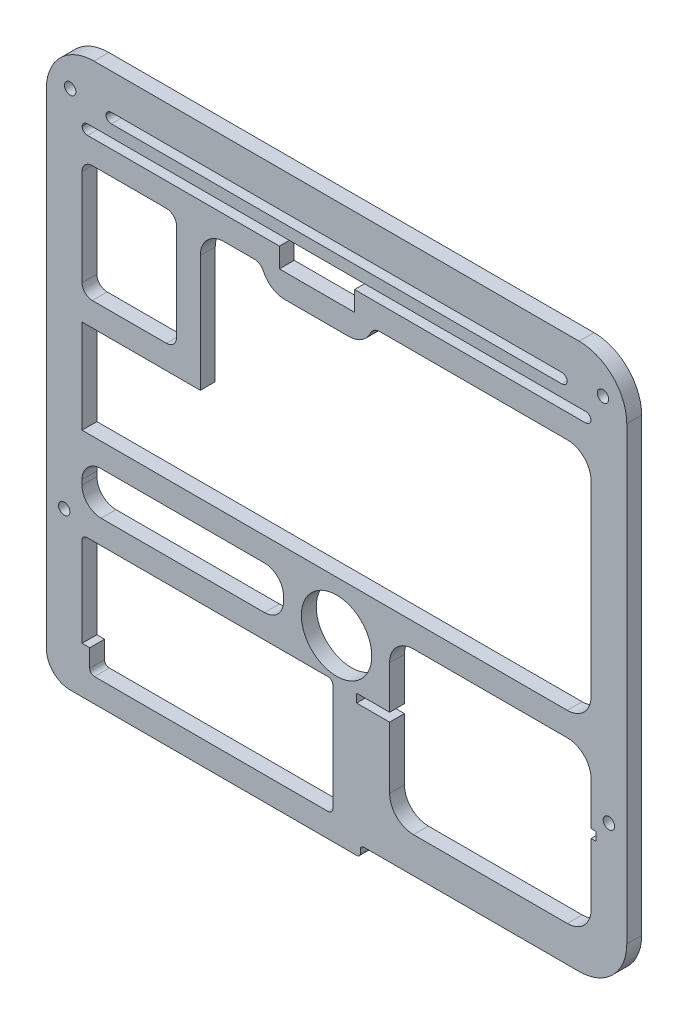
SolidWorks part; units mm, degrees
ref_plane "Front Plane" through (0, 0, 0) normal (0, 0, 1) x (1, 0, 0)
ref_plane "Top Plane" through (0, 0, 0) normal (0, 1, 0) x (1, 0, 0)
ref_plane "Right Plane" through (0, 0, 0) normal (1, 0, 0) x (0, 0, -1)
sketch "Sketch1" plane through (0, 0, 0) normal (0, 0, 1) x (1, 0, 0)
  line L0 (63.9883, 50.6392) -> (63.9883, 46.8292) construction
  line L1 (4.1102, -7.651) -> (66.0868, -7.651)
  line L2 (4.1102, -7.651) -> (4.1102, 50.6392)
  line L3 (4.1102, 50.6392) -> (66.0868, 50.6392)
  line L4 (66.0868, -7.651) -> (66.0868, 50.6392)
  line L5 (62.2768, 46.8292) -> (7.9202, 46.8292)
  line L6 (62.2768, 46.8292) -> (62.2768, -3.841)
  line L7 (62.2768, -3.841) -> (7.9202, -3.841)
  line L8 (7.9202, 46.8292) -> (7.9202, -3.841)
  line L9 (63.9883, 48.7342) -> (18.0707, 48.7342) construction
  line L10 (7.9202, 41.2855) -> (4.1102, 41.2855) construction
  line L11 (6.0152, 41.2855) -> (6.0152, 25.8577) construction
  line L12 (13.5248, -3.841) -> (13.5248, -7.651) construction
  line L13 (13.5248, -5.746) -> (21.1598, -5.746) construction
  line L14 (66.0868, 38.1916) -> (62.2768, 38.1916) construction
  line L15 (64.1818, 38.1916) -> (64.1818, 22.3321) construction
  line L16 (62.2768, 6.192) -> (62.2768, 41.7492) construction
  line L17 (7.9202, 36.7962) -> (7.9202, 1.239) construction
  line L22 (34.9556, 48.7342) -> (35.5018, 48.7342) construction
  line L23 (52.4244, -5.746) -> (51.8782, -5.746) construction
  dimension "D1" = 3.81
  dimension "D2" = 3.81
extrude "Boss-Extrude1" add sketch "Sketch1" along normal blind 1.5875
sketch "Sketch2" plane through (0, 0, 0) normal (0, 0, -1) x (-1, 0, 0)
  line L0 (-62.2768, -3.841) -> (-62.2768, 46.8292) construction
  line L1 (-62.2768, 15.868) -> (-7.9202, 15.868)
  line L2 (-62.2768, 15.868) -> (-62.2768, 13.328)
  line L3 (-62.2768, 13.328) -> (-7.9202, 13.328)
  line L4 (-7.9202, 15.868) -> (-7.9202, 13.328)
  line L5 (-7.9202, 46.8292) -> (-7.9202, -3.841) construction
  line L6 (-13.0532, 15.868) -> (-50.7532, 15.868) construction
  line L8 (-55.2788, 43.4256) -> (-16.9248, 43.4256) construction
  line L9 (-36.3812, 41.3174) -> (-29.6248, 41.3174) construction
  line L10 (-36.3812, 43.4256) -> (-36.3812, 41.3174) construction
  line L11 (-62.2768, 43.4256) -> (-37.0162, 43.4256)
  line L12 (-62.2768, 43.4256) -> (-62.2768, 40.8856)
  line L13 (-62.2768, 40.8856) -> (-38.9212, 40.8856)
  line L14 (-7.9202, 43.4256) -> (-7.9202, 40.8856)
  line L15 (-62.2768, 45.7624) -> (-7.9202, 45.7624)
  line L16 (-62.2768, 45.7624) -> (-62.2768, 44.4924)
  line L17 (-62.2768, 44.4924) -> (-7.9202, 44.4924)
  line L18 (-7.9202, 45.7624) -> (-7.9202, 44.4924)
  line L19 (-29.6248, 41.3174) -> (-29.6248, 43.4256) construction
  line L20 (-36.3812, 43.4256) -> (-36.3812, 41.3174) construction
  line L21 (-29.6248, 41.3174) -> (-29.6248, 43.4256) construction
  line L22 (-37.0162, 41.3174) -> (-37.0162, 43.4256)
  line L23 (-28.9898, 41.3174) -> (-37.0162, 41.3174)
  line L24 (-28.9898, 41.3174) -> (-28.9898, 43.4256)
  line L25 (-38.9212, 40.8856) -> (-38.9212, 38.7774)
  line L26 (-38.9212, 38.7774) -> (-27.0848, 38.7774)
  line L27 (-27.0848, 38.7774) -> (-27.0848, 40.8856)
  line L28 (-27.0848, 40.8856) -> (-7.9202, 40.8856)
  line L29 (-28.9898, 43.4256) -> (-7.9202, 43.4256)
  line L30 (-37.0162, 42.249) -> (-36.3812, 42.249) construction
  line L31 (-57.9086, 46.8292) -> (-57.9086, 45.7624) construction
  line L32 (-29.6248, 42.1673) -> (-28.9898, 42.1673) construction
  line L33 (-62.2768, 46.8292) -> (-7.9202, 46.8292) construction
  line L35 (-57.9086, 44.4924) -> (-57.9086, 43.4256) construction
  dimension "D1" = 2.54
  dimension "D2" = 1.905
  dimension "D3" = 2.54
  dimension "D4" = 1.905
  dimension "D5" = 1.27
  dimension "D6" = 0.635
extrude "Boss-Extrude2" add sketch "Sketch2" against normal up to surface (1.5875 mm away) up to face at (35.0985, 21.4941, 1.5875)
sketch "Sketch3" plane through (0, 0, 0) normal (0, 0, -1) x (-1, 0, 0)
  line L1 (-16.3032, 25.868) -> (-7.9202, 25.868) construction
  line L12 (-20.5532, 25.868) -> (-13.0532, 25.868)
  line L13 (-13.0532, 25.868) -> (-7.9202, 25.868)
  line L14 (-7.9202, 40.8856) -> (-7.9202, 15.868) construction
  line L15 (-7.9202, 25.868) -> (-7.9202, 28.408)
  line L16 (-7.9202, 28.408) -> (-18.0132, 28.408)
  line L17 (-18.0132, 28.408) -> (-18.0132, 40.8856)
  line L18 (-27.0848, 40.8856) -> (-7.9202, 40.8856) construction
  line L19 (-18.0132, 40.8856) -> (-20.5532, 40.8856)
  line L20 (-20.5532, 40.8856) -> (-20.5532, 25.868)
  line M27 (-27.0848, 40.8856) -> (-7.9202, 40.8856)
  line M28 (-7.9202, 40.8856) -> (-7.9202, 15.868)
  dimension "D3" = 2.54
  dimension "D4" = 2.54
extrude "Boss-Extrude3" add sketch "Sketch3" against normal up to surface (1.5875 mm away) contours L20 L12 L13 L16 L17 M27 M28 region at (20.3569, 33.3768, 0) up to face at (35.0985, 46.2958, 1.5875)
sketch "Sketch4" plane through (0, 0, 0) normal (0, 0, -1) x (-1, 0, 0)
  line L0 (-62.2768, 13.328) -> (-7.9202, 13.328) construction
  line L1 (-40.7627, 13.328) -> (-29.4343, 13.328)
  line L2 (-40.7627, 13.328) -> (-40.7627, -3.841)
  line L3 (-40.7627, -3.841) -> (-29.4343, -3.841)
  line L4 (-29.4343, 13.328) -> (-29.4343, -3.841)
  line L5 (-7.9202, -3.841) -> (-62.2768, -3.841) construction
  line L6 (-38.8577, 10.4578) -> (-40.7627, 10.4578) construction
  line L7 (-31.3393, 10.4578) -> (-29.4343, 10.4578) construction
  dimension "D1" = 1.905
extrude "Boss-Extrude4" add sketch "Sketch4" against normal up to surface (1.5875 mm away) up to face at (12.9667, 34.6468, 1.5875)
sketch "Sketch5" plane through (0, 0, 0) normal (0, 0, -1) x (-1, 0, 0)
  line L1 (-8.7364, -6.254) -> (-34.6952, -6.254) construction
  line L2 (-8.7364, -6.254) -> (-8.7364, 6.2047) construction
  line L6 (-8.7364, 6.2047) -> (-34.6952, 6.2047) construction
  line L7 (-34.6952, -6.254) -> (-34.6952, 6.2047) construction
  line L8 (-8.7364, -6.254) -> (-34.6952, -6.254)
  line L9 (-8.7364, -6.254) -> (-8.7364, 6.2047)
  line L10 (-8.7364, 6.2047) -> (-34.6952, 6.2047)
  line L11 (-34.6952, -6.254) -> (-34.6952, 6.2047)
  circle A1 centre (-35.0985, 10.4578) radius 3.7592 construction
  circle A2 centre (-35.0985, 10.4578) radius 3.7592
extrude "Cut-Extrude1" cut sketch "Sketch5" against normal up to surface (1.5875 mm away) up to face at (51.5197, 4.7435, 1.5875)
sketch "Sketch10" plane through (0, 0, 1.5875) normal (0, 0, 1) x (1, 0, 0)
  line L0 (29.4343, 13.328) -> (29.4343, 6.2047) construction
  line L1 (7.9202, 6.2047) -> (29.4343, 6.2047)
  line L2 (7.9202, 6.2047) -> (7.9202, 8.7447)
  line L3 (7.9202, 8.7447) -> (29.4343, 8.7447)
  line L4 (29.4343, 6.2047) -> (29.4343, 8.7447)
  line L5 (7.9202, 13.328) -> (7.9202, -3.841) construction
  line L6 (34.6952, 6.2047) -> (29.4343, 6.2047) construction
  dimension "D1" = 2.54
extrude "Boss-Extrude5" add sketch "Sketch10" against normal up to surface (1.5875 mm away) up to face at (20.1965, 2.3595, 0)
fillet "Fillet1" radius 5.08 3 edges at (66.0868, -7.651, 0.7937) (4.1102, 50.6392, 0.7937) (66.0868, 50.6392, 0.7937)
fillet "Fillet2" radius 2.54 5 edges at (20.5532, 40.8856, 0.7937) (27.0848, 38.7774, 0.7937) (62.2768, 40.8856, 0.7937) (62.2768, 15.868, 0.7937) (38.9212, 38.7774, 0.7937)
fillet "Fillet3" radius 1.0922 6 edges at (7.9202, 28.408, 0.7937) (18.0132, 28.408, 0.7937) (7.9202, 40.8856, 0.7937) (18.0132, 40.8856, 0.7937) (27.0848, 40.8856, 0.7937) (38.9212, 40.8856, 0.7937)
fillet "Fillet4" radius 0.5842 4 edges at (7.9202, 43.4256, 0.7937) (7.9202, 44.4924, 0.7937) (62.2768, 44.4924, 0.7937) (62.2768, 43.4256, 0.7937)
sketch "Sketch6" plane through (0, 0, 0) normal (0, 0, -1) x (-1, 0, 0)
  line L0 (-9.5532, 24.368) -> (-9.5532, 17.368) construction
  line L1 (-9.5532, 24.368) -> (-9.5532, 17.368)
  line L2 (-11.0532, 25.868) -> (-9.5532, 24.368) construction
  line L3 (-11.0532, 25.868) -> (-9.5532, 24.368)
  line L4 (-11.0532, 25.868) -> (-11.0532, 15.868)
  line L6 (-13.0532, 17.368) -> (-13.0532, 15.868)
  line L7 (-13.0532, 15.868) -> (-11.0532, 15.868)
  line L8 (-11.0532, 15.868) -> (-9.5532, 17.368)
  line L9 (-9.5532, 17.368) -> (-13.0532, 17.368)
  line L12 (-11.0532, 15.868) -> (-9.5532, 17.368)
  circle A0 centre (-63.5468, 46.8292) radius 0.6096 construction
  circle A1 centre (-6.6502, 46.8292) radius 0.6096 construction
  circle A2 centre (-64.1818, 7.6638) radius 0.6096 construction
  circle A3 centre (-6.0152, 7.6638) radius 0.6096 construction
  circle A4 centre (-63.5468, 46.8292) radius 0.6096
  circle A5 centre (-6.6502, 46.8292) radius 0.6096
  circle A6 centre (-64.1818, 7.6638) radius 0.6096
  circle A7 centre (-6.0152, 7.6638) radius 0.6096
  dimension "D1" = 0
extrude "Cut-Extrude2" cut sketch "Sketch6" against normal up to surface (1.5875 mm away) up to face at (17.1172, -1.2967, 1.5875)
sketch "Sketch9" plane through (0, 0, 1.5875) normal (0, 0, 1) x (1, 0, 0)
  line L4 (62.813, 6.2047) -> (37.2352, 6.2047)
  line L5 (37.2352, 6.2047) -> (37.2352, 5.2903)
  line L6 (37.2352, 5.2903) -> (62.813, 5.2903)
  line L7 (62.813, 5.2903) -> (62.813, 6.2047)
  line L8 (62.813, 6.2047) -> (37.2352, 6.2047)
  line L9 (37.2352, 6.2047) -> (37.2352, 5.2903)
  line L10 (37.2352, 5.2903) -> (62.813, 5.2903)
  line L11 (62.813, 5.2903) -> (62.813, 6.2047)
  dimension "D1" = 0
extrude "Cut-Extrude3" cut sketch "Sketch9" against normal up to surface (1.5875 mm away) up to face at (5.4056, 7.6638, 0)
fillet "Fillet6" radius 0.508 4 edges at (34.6952, 6.2047, 0.7937) (34.6952, -6.254, 0.7937) (8.7364, -6.254, 0.7937) (7.9202, 6.2047, 0.7937)
sketch "Sketch11" plane through (0, 0, 1.5875) normal (0, 0, 1) x (1, 0, 0)
  line L0 (9.2444, -6.254) -> (34.1872, -6.254) construction
  line L1 (4.1102, -7.651) -> (37.6385, -7.651)
  line L2 (4.1102, -7.651) -> (4.1102, -8.794)
  line L3 (4.1102, -8.794) -> (37.6385, -8.794)
  line L4 (37.6385, -7.651) -> (37.6385, -8.794)
  line L5 (35.0985, 14.217) -> (35.0985, -22.2214) construction
  circle A0 centre (35.0985, 10.4578) radius 3.7592 construction
  dimension "D1" = 2.54
  dimension "D2" = 2.54
extrude "Boss-Extrude6" add sketch "Sketch11" against normal up to surface (1.5875 mm away) up to face at (51.0212, 5.4129, 0)
fillet "Fillet7" radius 2.54 1 edges at (4.1102, -8.794, 0.7937)
fillet "Fillet8" radius 0.381 2 edges at (37.6385, -8.794, 0.7937) (37.6385, -7.651, 0.7937)
fillet "Fillet9" radius 2.032 4 edges at (29.4343, 8.7447, 0.7937) (29.4343, 13.328, 0.7937) (7.9202, 8.7447, 0.7937) (7.9202, 13.328, 0.7937)
fillet "Fillet10" radius 2.54 4 edges at (40.7627, -3.841, 0.7937) (62.2768, -3.841, 0.7937) (62.2768, 13.328, 0.7937) (40.7627, 13.328, 0.7937)
sketch "Sketch12" plane through (0, 0, 1.5875) normal (0, 0, 1) x (1, 0, 0)
  line L0 (7.9202, 46.8292) -> (7.9202, 45.7624) construction
  line L1 (7.9202, 46.8292) -> (10.4602, 46.8292)
  line L2 (7.9202, 46.8292) -> (7.9202, 45.7624)
  line L3 (7.9202, 45.7624) -> (10.4602, 45.7624)
  line L4 (10.4602, 46.8292) -> (10.4602, 45.7624)
  line L5 (62.2768, 46.8292) -> (7.9202, 46.8292) construction
  line L6 (62.2768, 45.7624) -> (7.9202, 45.7624) construction
  line L8 (62.2768, 46.8292) -> (59.7368, 46.8292)
  line L9 (62.2768, 46.8292) -> (62.2768, 45.7624)
  line L10 (62.2768, 45.7624) -> (59.7368, 45.7624)
  line L11 (59.7368, 46.8292) -> (59.7368, 45.7624)
  dimension "D1" = 2.54
extrude "Boss-Extrude7" add sketch "Sketch12" against normal up to surface (1.5875 mm away) up to face at (51.1458, 5.2455, 0)
fillet "Fillet11" radius 0.5842 4 edges at (59.7368, 45.7624, 0.7937) (59.7368, 46.8292, 0.7937) (10.4602, 45.7624, 0.7937) (10.4602, 46.8292, 0.7937)
